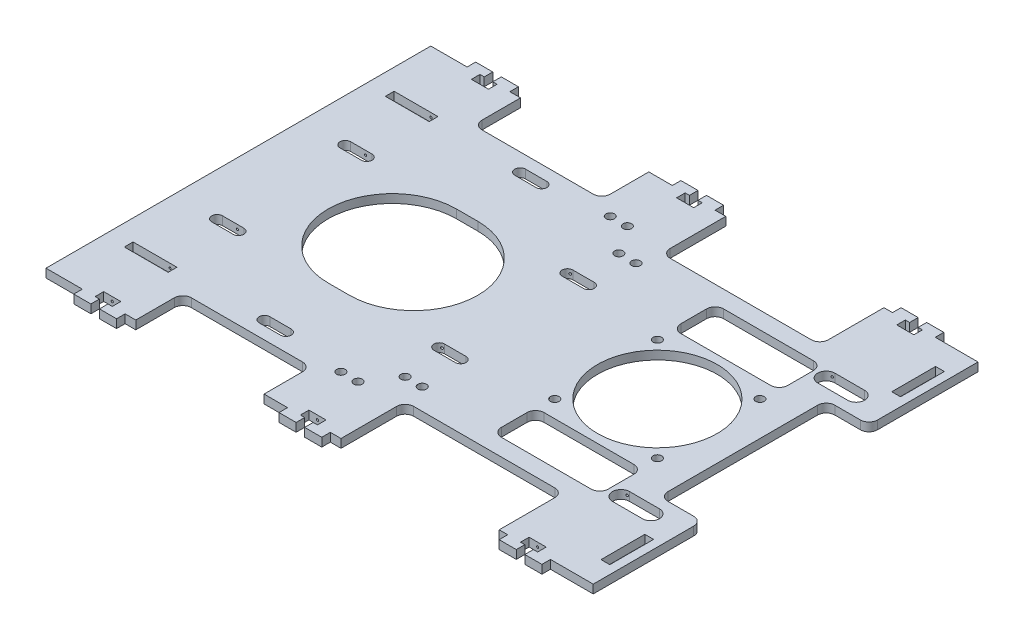
SolidWorks part; units mm, degrees
material "Сталь 13Х14НВРА ГОСТ 5632-72"
ref_plane "Спереди" through (0, 0, 0) normal (0, 0, 1) x (1, 0, 0)
ref_plane "Сверху" through (0, 0, 0) normal (0, 1, 0) x (1, 0, 0)
ref_plane "Справа" through (0, 0, 0) normal (1, 0, 0) x (0, 0, -1)
other "Configuration Table"
sketch "Эскиз1" plane through (0, 0, 0) normal (0, 1, 0) x (1, 0, 0)
  line L0 (0, -90) -> (290, -90) construction
  line L1 (0, 0) -> (17, 0)
  line L2 (0, 0) -> (0, -40)
  line L4 (256, 0) -> (256, -47)
  line L5 (37, 0) -> (42, 0)
  line L7 (17, 0) -> (17, 4)
  line L8 (17, 4) -> (25, 4)
  line L9 (37, 0) -> (37, 4)
  line L10 (29, 0) -> (31, 0)
  line L12 (25, 4) -> (25, 0)
  line L14 (29, 4) -> (29, 0)
  line L15 (23, 0) -> (25, 0)
  line L16 (23, 0) -> (23, -4)
  line L17 (23, -4) -> (31, -4)
  line L18 (31, 0) -> (31, -4)
  line L19 (29, 4) -> (37, 4)
  line L20 (123, -168) -> (123, 28.83) construction
  line L35 (228, -180) -> (230, -180)
  line L36 (236, -180) -> (236, -184)
  line L37 (236, -184) -> (228, -184)
  line L38 (216, -180) -> (216, -184)
  line L39 (228, -184) -> (228, -180)
  line L40 (224, -184) -> (224, -180)
  line L41 (222, -180) -> (224, -180)
  line L42 (230, -180) -> (230, -176)
  line L43 (230, -176) -> (222, -176)
  line L44 (222, -180) -> (222, -176)
  line L45 (224, -184) -> (216, -184)
  line L46 (29, -184) -> (37, -184)
  line L47 (31, -180) -> (31, -176)
  line L48 (23, -176) -> (31, -176)
  line L49 (23, -180) -> (23, -176)
  line L50 (23, -180) -> (25, -180)
  line L51 (29, -184) -> (29, -180)
  line L52 (25, -184) -> (25, -180)
  line L53 (29, -180) -> (31, -180)
  line L54 (37, -180) -> (37, -184)
  line L55 (17, -184) -> (25, -184)
  line L56 (17, -180) -> (17, -184)
  line L57 (0, -180) -> (17, -180)
  line L59 (236, -180) -> (256, -180)
  line L60 (30.25, -153.1) -> (30.25, -149)
  line L61 (9.75, -26.9) -> (30.25, -26.9)
  line L62 (9.75, -26.9) -> (9.75, -31)
  line L63 (9.75, -31) -> (30.25, -31)
  line L64 (30.25, -26.9) -> (30.25, -31)
  line L65 (9.75, -149) -> (30.25, -149)
  line L66 (9.75, -153.1) -> (9.75, -149)
  line L67 (9.75, -153.1) -> (30.25, -153.1)
  line L68 (133, 0) -> (138, 0)
  line L70 (113, 0) -> (113, 4)
  line L71 (113, 4) -> (121, 4)
  line L72 (133, 0) -> (133, 4)
  line L73 (125, 0) -> (127, 0)
  line L75 (121, 4) -> (121, 0)
  line L77 (125, 4) -> (125, 0)
  line L78 (119, 0) -> (121, 0)
  line L79 (119, 0) -> (119, -4)
  line L80 (119, -4) -> (127, -4)
  line L81 (127, 0) -> (127, -4)
  line L82 (125, 4) -> (133, 4)
  line L83 (125, -184) -> (133, -184)
  line L84 (127, -180) -> (127, -176)
  line L85 (119, -176) -> (127, -176)
  line L86 (119, -180) -> (119, -176)
  line L87 (119, -180) -> (121, -180)
  line L88 (125, -184) -> (125, -180)
  line L89 (121, -184) -> (121, -180)
  line L90 (125, -180) -> (127, -180)
  line L91 (133, -180) -> (133, -184)
  line L92 (113, -184) -> (121, -184)
  line L93 (113, -180) -> (113, -184)
  line L94 (37, -180) -> (42, -180)
  line L95 (133, -180) -> (138, -180)
  line L96 (72, -90) -> (82, -90) construction
  line L97 (72, -60) -> (82, -60)
  line L98 (72, -120) -> (82, -120)
  line L99 (77, -90) -> (18.6203, -56.2945) construction
  line L100 (77, -90) -> (77, -25.5481) construction
  line L101 (20.0385, -60) -> (30.0385, -60) construction
  line L102 (20.0385, -57.5) -> (30.0385, -57.5)
  line L103 (20.0385, -62.5) -> (30.0385, -62.5)
  line L104 (133.9615, -59.9967) -> (123.9615, -60.0033) construction
  line L105 (133.9599, -57.4967) -> (123.9599, -57.5033)
  line L106 (133.9632, -62.4967) -> (123.9632, -62.5033)
  line L107 (20.0385, -120) -> (30.0385, -120) construction
  line L108 (20.0385, -122.5) -> (30.0385, -122.5)
  line L109 (20.0385, -117.5) -> (30.0385, -117.5)
  line L110 (133.9615, -120) -> (123.9615, -120) construction
  line L111 (133.9615, -122.5) -> (123.9615, -122.5)
  line L112 (133.9615, -117.5) -> (123.9615, -117.5)
  line L113 (82, -30.2087) -> (72, -30.2087) construction
  line L114 (82, -32.7087) -> (72, -32.7087)
  line L115 (82, -27.7087) -> (72, -27.7087)
  line L116 (82, -149.7913) -> (72, -149.7913) construction
  line L117 (82, -147.2913) -> (72, -147.2913)
  line L118 (82, -152.2913) -> (72, -152.2913)
  line L119 (221, -138) -> (221, -126)
  line L120 (175, -38) -> (217, -38)
  line L121 (171, -42) -> (171, -54)
  line L122 (175, -58) -> (217, -58)
  line L123 (221, -42) -> (221, -54)
  line L124 (175, -122) -> (217, -122)
  line L125 (171, -138) -> (171, -126)
  line L126 (175, -142) -> (217.0114, -142)
  line L127 (256, -133) -> (256, -180)
  line L128 (240, -51) -> (252, -51)
  line L129 (236, -55) -> (236, -125)
  line L130 (240, -129) -> (252, -129)
  line L132 (227, -42) -> (241, -42) construction
  line L133 (227, -38) -> (241, -38)
  line L134 (227, -46) -> (241, -46)
  line L135 (227, -138) -> (241, -138) construction
  line L136 (227, -142) -> (241, -142)
  line L137 (227, -134) -> (241, -134)
  line L138 (247.9, -147.75) -> (252, -147.75)
  line L139 (247.9, -11.75) -> (252, -11.75)
  line L140 (247.9, -11.75) -> (247.9, -32.25)
  line L141 (247.9, -32.25) -> (252, -32.25)
  line L142 (252, -11.75) -> (252, -32.25)
  line L143 (247.9, -168.25) -> (252, -168.25)
  line L144 (247.9, -168.25) -> (247.9, -147.75)
  line L145 (252, -168.25) -> (252, -147.75)
  line L149 (46, -22) -> (98, -22)
  line L150 (102, 0) -> (102, -18)
  line L162 (0, -140) -> (0, -180)
  line L170 (0, -40) -> (0, -140)
  line L171 (42, -18) -> (42, 0)
  line L172 (102, 0) -> (113, 0)
  line L173 (236, 0) -> (236, 4)
  line L174 (236, 4) -> (228, 4)
  line L175 (228, 4) -> (228, 0)
  line L176 (228, 0) -> (230, 0)
  line L177 (230, 0) -> (230, -4)
  line L178 (230, -4) -> (222, -4)
  line L179 (224, 4) -> (224, 0)
  line L180 (222, 0) -> (224, 0)
  line L181 (222, 0) -> (222, -4)
  line L182 (224, 4) -> (216, 4)
  line L183 (216, 0) -> (216, 4)
  line L184 (236, 0) -> (256, 0)
  line L185 (212, 0) -> (216, 0)
  line L187 (138, 0) -> (138, -26)
  line L188 (142, -30) -> (208, -30)
  line L189 (212, 0) -> (212, -26)
  line L190 (212, -180) -> (212, -154)
  line L191 (142, -150) -> (208, -150)
  line L192 (138, -180) -> (138, -154)
  line L193 (102, -180) -> (102, -162)
  line L194 (46, -158) -> (98, -158)
  line L195 (42, -162) -> (42, -180)
  line L196 (102, -180) -> (113, -180)
  line L197 (212, -180) -> (216, -180)
  line L198 (77, -90) -> (128.9615, -60) construction
  line L199 (77, -90) -> (128.9615, -120) construction
  line L200 (128.9615, -120) -> (25.0385, -120) construction
  line L201 (25.0385, -120) -> (77, -90) construction
  arc A0 (72, -60) -> (72, -120) centre (72, -90) ccw
  arc A1 (82, -120) -> (82, -60) centre (82, -90) ccw
  circle A2 centre (77, -90) radius 60 construction
  arc A3 (20.0385, -57.5) -> (20.0385, -62.5) centre (20.0385, -60) ccw
  arc A4 (30.0385, -62.5) -> (30.0385, -57.5) centre (30.0385, -60) ccw
  arc A5 (133.9599, -57.4967) -> (133.9632, -62.4967) centre (133.9615, -59.9967) cw
  arc A6 (123.9632, -62.5033) -> (123.9599, -57.5033) centre (123.9615, -60.0033) cw
  arc A7 (20.0385, -122.5) -> (20.0385, -117.5) centre (20.0385, -120) cw
  arc A8 (30.0385, -117.5) -> (30.0385, -122.5) centre (30.0385, -120) cw
  arc A9 (133.9615, -122.5) -> (133.9615, -117.5) centre (133.9615, -120) ccw
  arc A10 (123.9615, -117.5) -> (123.9615, -122.5) centre (123.9615, -120) ccw
  arc A11 (82, -32.7087) -> (82, -27.7087) centre (82, -30.2087) ccw
  arc A12 (72, -27.7087) -> (72, -32.7087) centre (72, -30.2087) ccw
  arc A13 (82, -147.2913) -> (82, -152.2913) centre (82, -149.7913) cw
  arc A14 (72, -152.2913) -> (72, -147.2913) centre (72, -149.7913) cw
  circle A15 centre (196, -90) radius 28
  circle A16 centre (172, -66) radius 2
  circle A17 centre (220, -66) radius 2
  circle A18 centre (220, -114) radius 2
  circle A19 centre (172, -114) radius 2
  arc A20 (171, -54) -> (175, -58) centre (175, -54) ccw
  arc A21 (217, -58) -> (221, -54) centre (217, -54) ccw
  arc A22 (217, -38) -> (221, -42) centre (217, -42) cw
  arc A23 (175, -38) -> (171, -42) centre (175, -42) ccw
  arc A24 (171, -126) -> (175, -122) centre (175, -126) cw
  arc A25 (175, -142) -> (171, -138) centre (175, -138) cw
  arc A26 (217.0114, -142) -> (221, -138) centre (217, -138) ccw
  arc A27 (217, -122) -> (221, -126) centre (217, -126) cw
  arc A28 (240, -51) -> (236, -55) centre (240, -55) ccw
  arc A29 (236, -125) -> (240, -129) centre (240, -125) ccw
  arc A30 (252, -129) -> (256, -133) centre (252, -133) cw
  arc A31 (252, -51) -> (256, -47) centre (252, -47) ccw
  arc A32 (227, -38) -> (227, -46) centre (227, -42) ccw
  arc A33 (241, -46) -> (241, -38) centre (241, -42) ccw
  arc A34 (227, -142) -> (227, -134) centre (227, -138) cw
  arc A35 (241, -134) -> (241, -142) centre (241, -138) cw
  arc A40 (42, -18) -> (46, -22) centre (46, -18) ccw
  arc A41 (98, -22) -> (102, -18) centre (98, -18) ccw
  circle A44 centre (128, -140) radius 2
  circle A45 centre (136, -140) radius 2
  circle A46 centre (136, -40) radius 2
  circle A47 centre (128, -40) radius 2
  circle A48 centre (110.9615, -153) radius 2
  circle A49 centre (118.9615, -153) radius 2
  circle A50 centre (118.9615, -27) radius 2
  circle A51 centre (110.9615, -27) radius 2
  arc A52 (208, -30) -> (212, -26) centre (208, -26) ccw
  arc A53 (138, -26) -> (142, -30) centre (142, -26) ccw
  arc A54 (208, -150) -> (212, -154) centre (208, -154) cw
  arc A55 (138, -154) -> (142, -150) centre (142, -154) cw
  arc A56 (98, -158) -> (102, -162) centre (98, -162) cw
  arc A57 (42, -162) -> (46, -158) centre (46, -162) cw
  point P77 (121, 2)
  point P92 (77, -90)
  point P103 (25.0385, -60)
  point P108 (77, -30.2087)
  point P113 (128.9615, -60)
  point P120 (25.0385, -120)
  point P127 (128.9615, -120)
  point P140 (77, -149.7913)
  point P163 (221, -38)
  point P166 (171, -38)
  point P187 (236, -129)
  point P190 (256, -129)
  point P195 (234, -42)
  point P202 (234, -138)
  point P225 (138, -30)
  point P226 (100, -158)
  point P238 (39.9992, -22)
  point P241 (102, -22)
  dimension "D28" = 30
  dimension "D33" = 56
  dimension "D35" = 4
  dimension "D38" = 2
  dimension "D44" = 4
  dimension "D48" = 4
  dimension "D61" = 8
  dimension "D64" = 4
  dimension "D65" = 4
  dimension "D66" = 2
  dimension "D70" = 40
  dimension "D68" = 4
  dimension "D71" = 8
  dimension "D60" = 4
  dimension "D1" = 180
  dimension "D2" = 256
  dimension "D3" = 17
  dimension "D4" = 20
  dimension "D5" = 4
  dimension "D6" = 8
  dimension "D7" = 4
  dimension "D8" = 4
  dimension "D9" = 2
  dimension "D10" = 2
  dimension "D11" = 4.1
  dimension "D12" = 35
  dimension "D13" = 20.5
  dimension "D14" = 9.75
  dimension "D15" = 20
  dimension "D16" = 10
  dimension "D17" = 123
  dimension "D18" = 4
  dimension "D19" = 4
  dimension "D20" = 8
  dimension "D21" = 4
  dimension "D22" = 4
  dimension "D23" = 2
  dimension "D24" = 2
  dimension "D25" = 10
  dimension "D26" = 60
  dimension "D27" = 72
  dimension "D29" = 5
  dimension "D30" = 10
  dimension "D31" = 5
  dimension "D32" = 10
  dimension "D34" = 60
  dimension "D36" = 24
  dimension "D37" = 24
  dimension "D40" = 20
  dimension "D41" = 32
  dimension "D42" = 25
  dimension "D43" = 50
  dimension "D45" = 30
  dimension "D46" = 51
  dimension "D47" = 20
  dimension "D49" = 8
  dimension "D50" = 14
  dimension "D51" = 74
  dimension "D52" = 22
  dimension "D53" = 20.5
  dimension "D54" = 4.1
  dimension "D55" = 4
  dimension "D56" = 44
  dimension "D57" = 22
  dimension "D58" = 42
  dimension "D59" = 60
  dimension "D62" = 20
  dimension "D63" = 8
  dimension "D67" = 8
  dimension "D69" = 8
  dimension "D72" = 27
  dimension "D73" = 2
  dimension "D74" = 2
  dimension "D75" = 4
  dimension "D76" = 4
  dimension "D77" = 4
  dimension "D78" = 20
  dimension "D79" = 20
  dimension "D80" = 8
  dimension "D81" = 4
  dimension "D82" = 20
  dimension "D83" = 4
  dimension "D84" = 4
  dimension "D85" = 2
  dimension "D86" = 2
  dimension "D87" = 20
  dimension "D88" = 90
  dimension "D89" = 50
  dimension "D90" = 11.75
  dimension "D91" = 11.75
  dimension "D92" = 20.5
  dimension "D93" = 60
  dimension "D94" = 10
  dimension "D95" = 10
  dimension "D96" = 60
  dimension "D97" = 30
  dimension "D98" = 30
  dimension "D99" = 20
  dimension "D100" = 32
  dimension "D39" = 2
base flange "Базовая кромка1" sketch "Эскиз1" thickness 4 reverse thickness direction no parameters "D1"=0.7366
sketch "Эскиз2" plane through (0, 0, 180) normal (0, 0, 1) x (1, 0, 0)
  line L0 (23, 0) -> (31, 0) construction
  line L1 (25, -4) -> (25, 0) construction
  line L2 (121, -4) -> (121, 0) construction
  line L3 (224, -4) -> (224, 0) construction
  circle A0 centre (27, -2) radius 0.5
  circle A1 centre (123, -2) radius 0.5
  circle A2 centre (226, -2) radius 0.5
  dimension "D3" = 1
  dimension "D4" = 1
  dimension "D7" = 1
  dimension "D1" = 2
  dimension "D2" = 2
  dimension "D5" = 2
  dimension "D6" = 2
extrude "Вырез-Вытянуть3" cut sketch "Эскиз2" against normal through all normal cut yes
sketch "Сгиб-Линии1" [suppressed] plane through (0, 0, 0) normal (0, 1, 0) x (1, 0, 0)
sketch "Граничная рамка1" [suppressed] plane through (0, 0, 0) normal (0, 1, 0) x (1, 0, 0)
sheet metal parameters "Листовой металл3" thickness 4 parameters "D1"=0.7366
flat pattern "Развертка3" [suppressed]
sketch "Сгиб-Линии2" plane through (0, 0, 0) normal (0, 1, 0) x (1, 0, 0)
sketch3d "Граничная рамка2" [suppressed]
  line L0 (290, -172, 0) -> (0, -172, 0) construction
  line L1 (290, 4, 0) -> (0, 4, 0) construction
  line L2 (290, -172, 0) -> (290, 4, 0) construction
  line L3 (0, -172, 0) -> (0, 4, 0) construction
sheet metal parameters "Листовой металл5" thickness 4 parameters "D1"=0.7366
flat pattern "Развертка3"
sketch "Сгиб-Линии2" plane through (0, 0, 0) normal (0, 1, 0) x (1, 0, 0)
sketch3d "Граничная рамка2" [suppressed]
  line L0 (210, 166, 0) -> (-46, 166, 0) construction
  line L1 (210, -22, 0) -> (-46, -22, 0) construction
  line L2 (210, 166, 0) -> (210, -22, 0) construction
  line L3 (-46, 166, 0) -> (-46, -22, 0) construction
